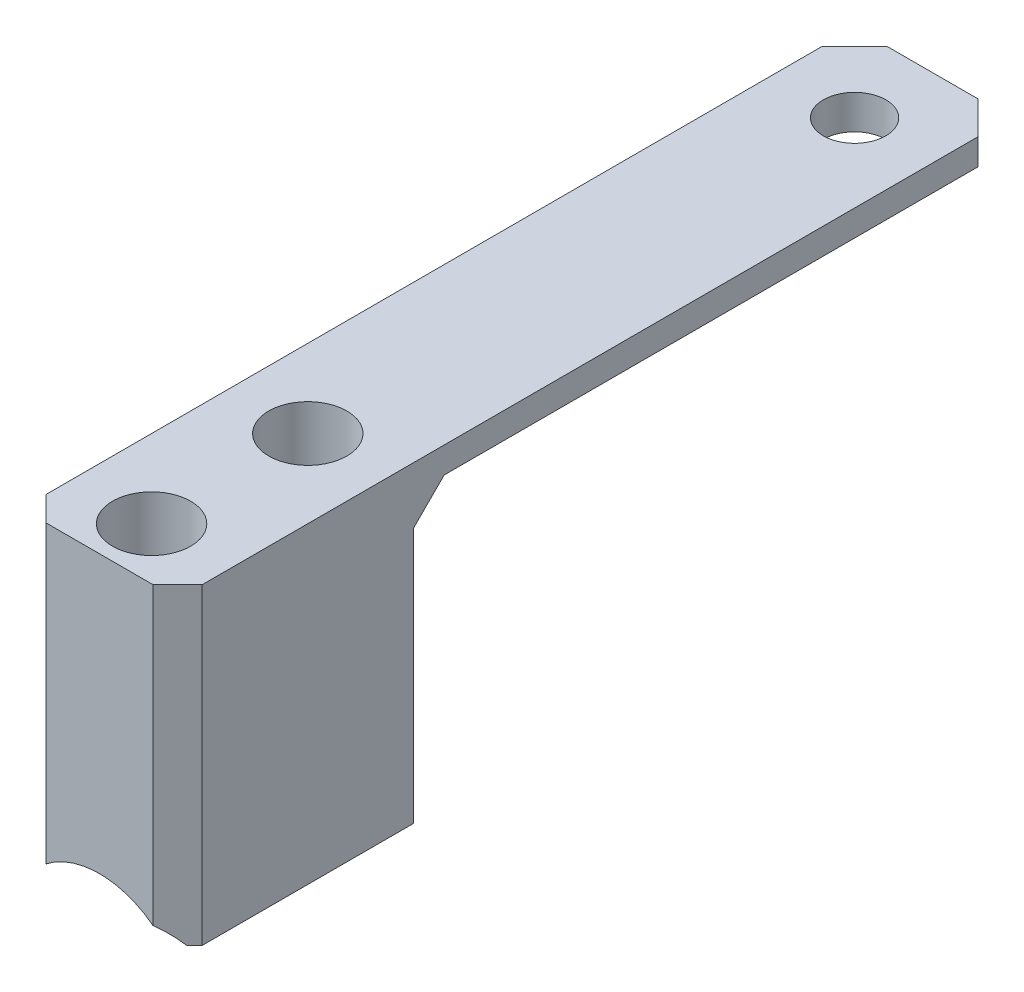
SolidWorks part; units mm, degrees
ref_plane "Front Plane" through (0, 0, 0) normal (0, 0, 1) x (1, 0, 0)
ref_plane "Top Plane" through (0, 0, 0) normal (0, 1, 0) x (1, 0, 0)
ref_plane "Right Plane" through (0, 0, 0) normal (1, 0, 0) x (0, 0, -1)
sketch "Sketch1" plane through (0, 0, 0) normal (0, 1, 0) x (1, 0, 0)
  line L0 (-9.525, -19.05) -> (9.525, -19.05)
  line L1 (9.525, -50.8) -> (-9.525, -50.8)
  line L2 (9.525, -50.8) -> (9.525, 46.8)
  line L3 (5.525, 50.8) -> (-5.525, 50.8)
  line L4 (-9.525, -50.8) -> (-9.525, 46.8)
  line L5 (9.525, -50.8) -> (-9.525, 50.8) construction
  line L6 (9.525, 50.8) -> (-9.525, -50.8) construction
  line L7 (0, 50.8) -> (0, -50.8) construction
  line L8 (9.525, 46.8) -> (-9.525, 46.8) construction
  line L9 (-9.525, 46.8) -> (-5.525, 50.8)
  line L10 (9.525, 46.8) -> (5.525, 50.8)
  circle A0 centre (0, -25.4) radius 3.175
  circle A1 centre (0, -44.45) radius 3.175
  point P0 (0, 0)
  dimension "D6" = 6.35
  dimension "D8" = 4
  dimension "D1" = 19.05
  dimension "D2" = 101.6
  dimension "D3" = 31.75
  dimension "D5" = 6.35
  dimension "D7" = 4
  dimension "D4" = 2
extrude "Boss-Extrude1" add sketch "Sketch1" against normal blind 38.1 contours L4 L1 L2 L0 region at (0, 0, 34.925)
extrude "Boss-Extrude4" add sketch "Sketch1<8>" against normal blind 3.175 contours L4 L0 L2 L3 region at (0, 0, -15.4662)
sketch "Sketch1<8>" plane through (0, 0, 0) normal (0, 1, 0) x (1, 0, 0) same geometry as "Sketch1"
sketch "Sketch2" plane through (0, 0, 0) normal (0, 1, 0) x (1, 0, 0)
  circle A0 centre (0, -25.4) radius 4.7625
  circle A1 centre (0, -44.45) radius 4.7625
  dimension "D2" = 9.525
  dimension "D1" = 2
extrude "Cut-Extrude1" cut sketch "Sketch2" against normal blind 25.4
chamfer "Chamfer1" distance 5 distance2 5 1 edges
chamfer "Chamfer2" distance 3 angle 45 6 edges at (-9.525, -19.05, 50.8) (9.525, -19.05, 50.8) (-9.525, -5.675, 16.55) (9.525, -5.675, 16.55)
sketch "Sketch3" plane through (0, 0, 50.8) normal (0, 0, 1) x (1, 0, 0)
  line L0 (0, 0) -> (0, -44.45) construction
  circle A0 centre (0, -44.45) radius 10.67
  dimension "D1" = 44.45
extrude "Cut-Extrude2" cut sketch "Sketch3" against normal through all
sketch "Sketch6" plane through (0, -3.175, 0) normal (0, -1, 0) x (1, 0, 0)
  circle A0 centre (0, -41.275) radius 3.81
  circle A1 centre (0, -41.275) radius 5.81
  dimension "D1" = 7.62
  dimension "D2" = 9.525
  dimension "D3" = 2
extrude "Cut-Extrude3" cut sketch "Sketch6" against normal blind 5.175 contours A0
extrude "Boss-Extrude6" add sketch "Sketch6<3>" along normal blind 1
sketch "Sketch6<3>" plane through (0, -3.175, 0) normal (0, -1, 0) x (1, 0, 0) same geometry as "Sketch6"
chamfer "Chamfer3" distance 1 angle 45 1 edges at (0, -3.175, -35.465)
